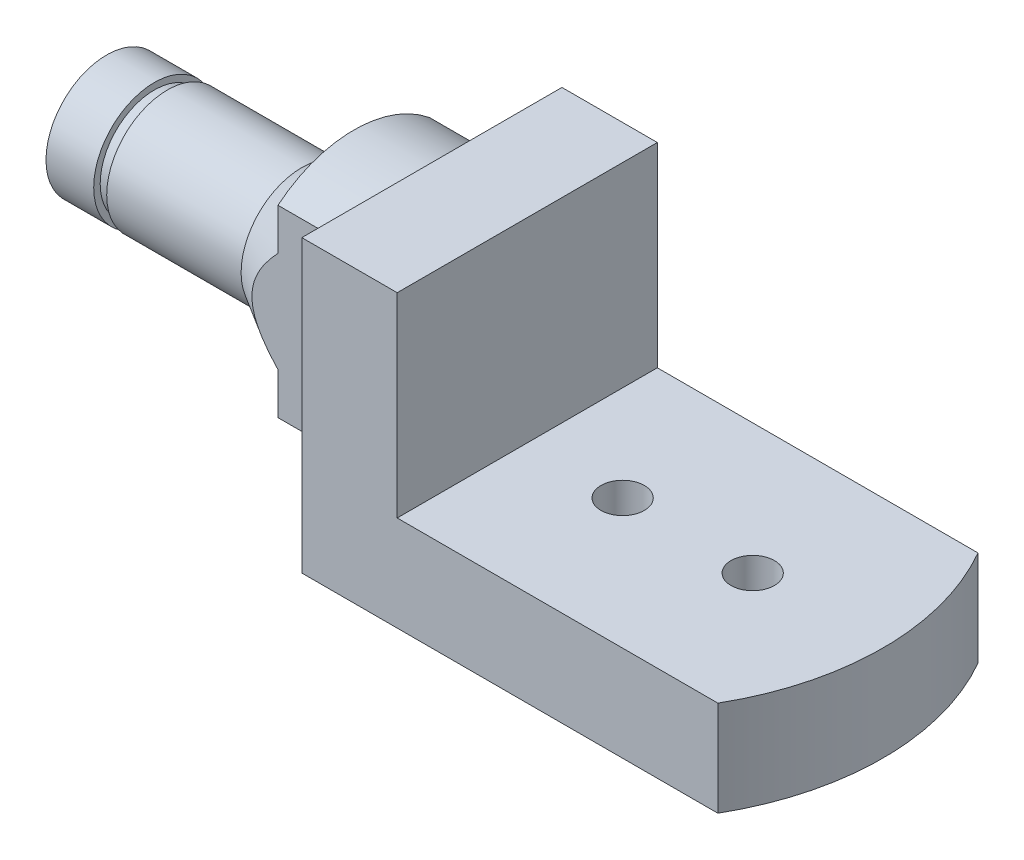
SolidWorks part; units mm, degrees
ref_plane "Front Plane" through (0, 0, 0) normal (0, 0, 1) x (1, 0, 0)
ref_plane "Top Plane" through (0, 0, 0) normal (0, 1, 0) x (1, 0, 0)
ref_plane "Right Plane" through (0, 0, 0) normal (1, 0, 0) x (0, 0, -1)
sketch "Sketch1" plane through (0, 0, 0) normal (0, 1, 0) x (1, 0, 0)
  line L0 (-22, -30) -> (-44, -30)
  line L1 (0, -30) -> (51.9615, -30)
  line L2 (0, 30) -> (51.9615, 30)
  line L4 (-22, 0) -> (-22, 30)
  line L5 (-22, 30) -> (0, 30)
  line L6 (-22, 0) -> (-22, -30)
  line L7 (-22, -30) -> (0, -30)
  line L8 (-44, -30) -> (-44, 30)
  line L9 (-44, 30) -> (-22, 30)
  arc A0 (51.9615, -30) -> (51.9615, 30) centre (0, 0) ccw
  circle A1 centre (30, 0) radius 5
  point P8 (0, 0)
extrude "Boss-Extrude1" add sketch "Sketch1" along normal blind 22 contours L1 A0 L2 L5 L4 L6 L7 A1 region at (17.5281, 0, 0)
extrude "Boss-Extrude2" add sketch "Sketch1<3>" along normal blind 67 contours L9 L8 L0 L6 L4 region at (-33, 0, 0)
sketch "Sketch1<3>" plane through (0, 0, 0) normal (0, 1, 0) x (1, 0, 0) same geometry as "Sketch1"
sketch "Sketch2" plane through (-44, 0, 0) normal (-1, 0, 0) x (0, 0, 1)
  line L0 (0, 0) -> (0, 37)
  circle A0 centre (0, 37) radius 27.5
extrude "Boss-Extrude3" add sketch "Sketch2" along normal blind 18 contours A0 region at (-44, 18.1046, 18.8954)
ref_plane "Plane1" through (0, 0, 0) normal (0, 0, 1) x (1, 0, 0)
sketch "Sketch3" plane through (0, 0, 0) normal (0, 0, 1) x (1, 0, 0)
  line L1 (-62, 37) -> (-74, 37)
  line L2 (-74, 37) -> (-74, 51)
  line L4 (-62, 37) -> (-62, 58)
  line L5 (-62, 58) -> (-74, 51)
revolve "Revolve2" add sketch "Sketch3" angle 360 about L1
sketch "Sketch5" plane through (-74, 0, 0) normal (-1, 0, 0) x (0, 0, 1)
  circle A1 centre (0, 37) radius 14
extrude "Boss-Extrude5" add sketch "Sketch5" along normal blind 31
sketch "Sketch6" plane through (-105, 0, 0) normal (-1, 0, 0) x (0, 0, 1)
  circle A0 centre (0, 37) radius 12.5
extrude "Boss-Extrude6" add sketch "Sketch6" along normal blind 3
sketch "Sketch7" plane through (-108, 0, 0) normal (-1, 0, 0) x (0, 0, 1)
  circle A0 centre (0, 37) radius 14
extrude "Boss-Extrude7" add sketch "Sketch7" along normal blind 11
sketch "Sketch8" plane through (0, 0, 30) normal (0, 0, 1) x (1, 0, 0)
  line L0 (-44, 67) -> (-74, 67)
  line L1 (-74, 67) -> (-74, 0)
  line L2 (-74, 0) -> (-44, 0)
  line L3 (-44, 0) -> (-44, 67)
extrude "Cut-Extrude1" cut sketch "Sketch8" against normal blind 12.5
mirror "Mirror1" about plane through (0, 0, 0) normal (0, 0, 1) of "Cut-Extrude1"
sketch "Sketch9" plane through (0, 22, 0) normal (0, 1, 0) x (1, 0, 0)
  circle A0 centre (0, 0) radius 5
extrude "Cut-Extrude2" cut sketch "Sketch9" against normal blind 32.5
